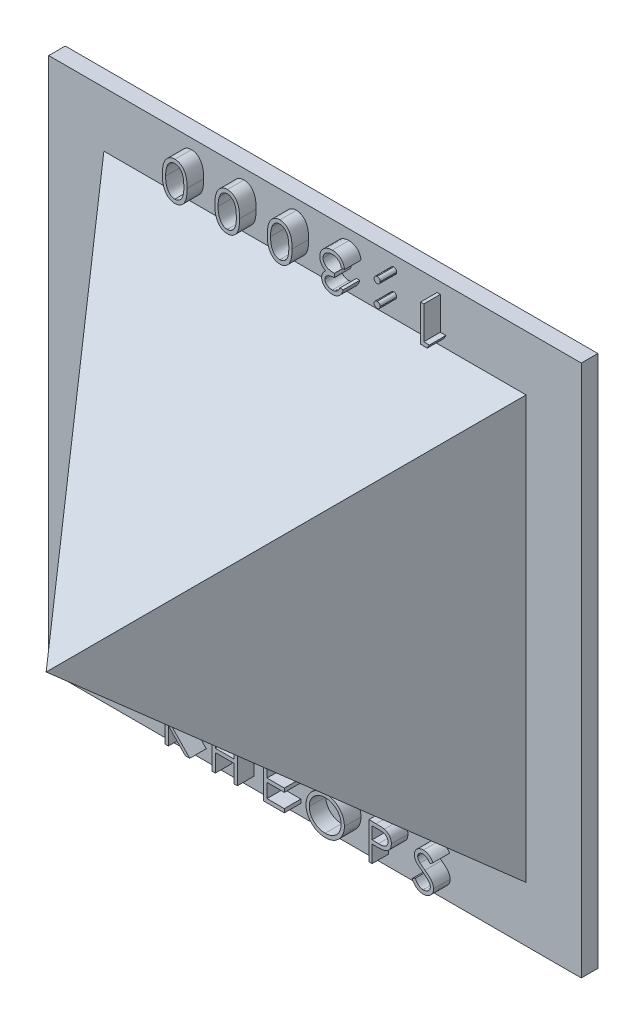
SolidWorks part; units mm, degrees
ref_plane "Plan de face" through (0, 0, 0) normal (0, 0, 1) x (1, 0, 0)
ref_plane "Plan de dessus" through (0, 0, 0) normal (0, 1, 0) x (1, 0, 0)
ref_plane "Plan de droite" through (0, 0, 0) normal (1, 0, 0) x (0, 0, -1)
sketch "Esquisse1" plane through (0, 0, 0) normal (0, 0, 1) x (1, 0, 0)
  line L1 (0, 0) -> (76.5, 0)
  line L2 (0, 0) -> (0, 76.5)
  line L3 (0, 76.5) -> (76.5, 76.5)
  line L4 (76.5, 0) -> (76.5, 76.5)
  dimension "D1" = 76.5
extrude "Boss.-Extru.1" add sketch "Esquisse1" along normal blind 97.7 draft 38.14
sketch "Esquisse3" plane through (0, 0, 0) normal (0, 0, -1) x (-1, 0, 0)
  line L8 (10, -10) -> (10, 86.5)
  line L9 (10, 86.5) -> (-86.5, 86.5)
  line L10 (-86.5, 86.5) -> (-86.5, -10)
  line L11 (-86.5, -10) -> (10, -10)
  line L12 (10, -10) -> (10, 86.5)
  line L13 (10, 86.5) -> (-86.5, 86.5)
  line L14 (-86.5, 86.5) -> (-86.5, -10)
  line L15 (-86.5, -10) -> (10, -10)
  dimension "D1" = 10
extrude "Boss.-Extru.3" add sketch "Esquisse3" along normal blind 3 separate body
sketch "Esquisse2" plane through (0, 0, -3) normal (0, 0, -1) x (-1, 0, 0)
  line L0 (0, 0) -> (-76.5, 0) construction
  line L1 (0, 76.5) -> (0, 0) construction
  circle A0 centre (-38.25, 38.25) radius 24
  point P5 (-38.25, 0)
  point P8 (0, 38.25)
  dimension "D1" = 48
extrude "Boss.-Extru.2" [suppressed] add sketch "Esquisse2" along normal blind 30
sketch "Esquisse4" plane through (0, 0, 0) normal (0, 0, 1) x (1, 0, 0)
  line L0 (13.25, -8) -> (63.25, -8) construction
  line L2 (86.5, -10) -> (-10, -10) construction
  line L3 (13.25, 84.5) -> (63.25, 84.5) construction
  line L6 (-10, 86.5) -> (86.5, 86.5) construction
  line L7 (76.5, 76.5) -> (0, 76.5) construction
  line L8 (0, 0) -> (76.5, 0) construction
  text T0 "KHEOPS" font "Century Gothic" height in points 25
  text T1 "1:3000\r\n" font "Century Gothic" height in points 25
  point P4 (38.25, 0)
  point P5 (38.25, -8)
  point P15 (38.25, 76.5)
  point P16 (38.25, 84.5)
  point P17 (12.2512, -8)
  dimension "D1" = 2
  dimension "D2" = 2
  dimension "D3" = 50
  dimension "D4" = 50
extrude "Boss.-Extru.4" add sketch "Esquisse4" along normal blind 3
